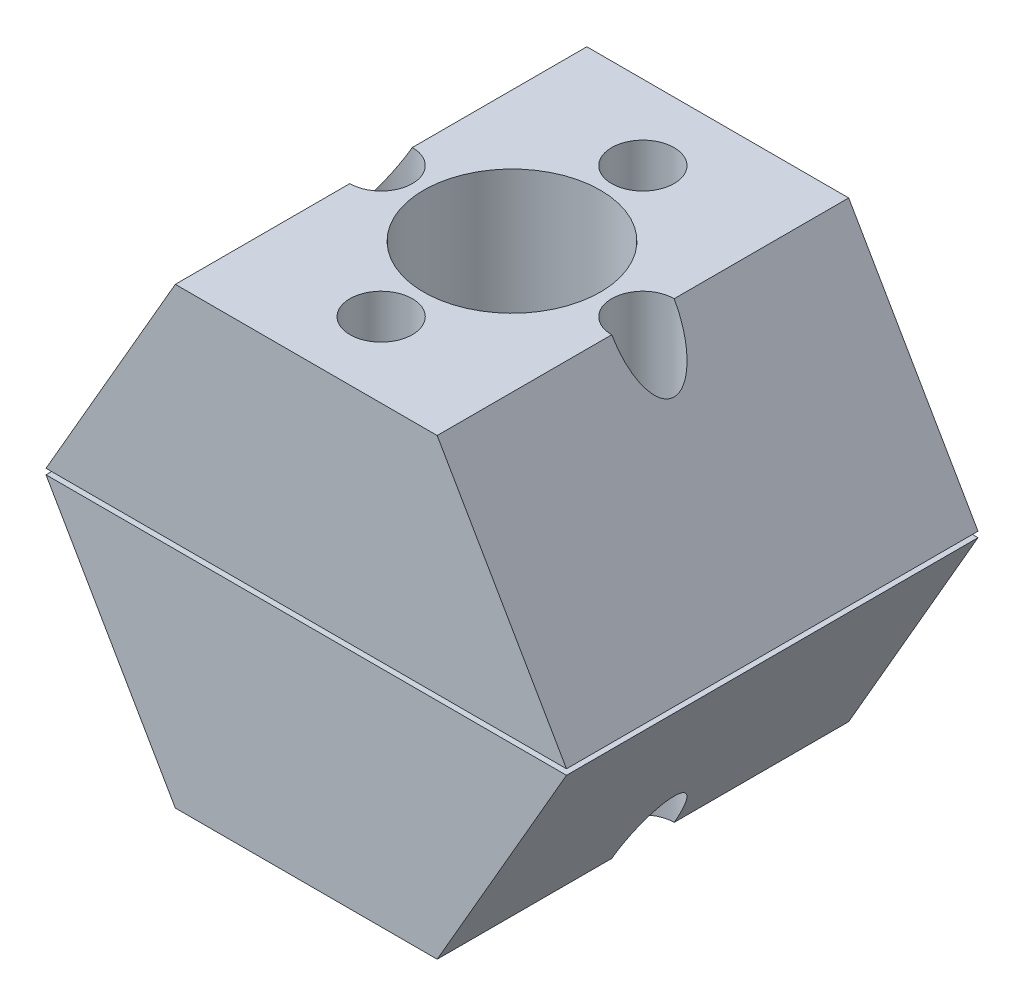
SolidWorks part; units mm, degrees
note: The reader was unsure of these and kept them because the rebuilt part matched: shared geometry of "Sketch1<6>", "Sketch1<7>", "Sketch4<6>", "Sketch3<3>".
ref_plane "Front Plane" through (0, 0, 0) normal (0, 0, 1) x (1, 0, 0)
ref_plane "Top Plane" through (0, 0, 0) normal (0, 1, 0) x (1, 0, 0)
ref_plane "Right Plane" through (0, 0, 0) normal (1, 0, 0) x (0, 0, -1)
sketch "Sketch1" plane through (0, 0, 0) normal (0, 0, 1) x (1, 0, 0)
  line L0 (0, 0) -> (0, 15.5) construction
  line L1 (-5.451, 5.581) -> (-5.451, 15.881)
  line L2 (9.735, 1.5) -> (9.735, 5.2) construction
  line L3 (-5.451, 15.881) -> (5.451, 15.881)
  line L5 (5.451, 15.881) -> (5.451, 5.581)
  line L6 (5.451, 5.581) -> (11.381, 5.581)
  line L7 (11.381, 1.119) -> (11.381, 3.1595)
  line L11 (8.035, 5.2) -> (8.035, 1.5) construction
  line L23 (-9.735, 5.2) -> (-9.735, 1.5) construction
  line L32 (11.381, 1.119) -> (5.451, 1.119)
  line L33 (5.451, -0.381) -> (5.451, 1.119)
  line L34 (5.451, -0.381) -> (-5.451, -0.381)
  line L39 (-5.451, -0.381) -> (-5.451, 1.119)
  line L42 (-5.451, 1.119) -> (-11.381, 1.119)
  line L46 (-11.381, 1.119) -> (-11.381, 3.1595)
  line L47 (-11.381, 5.581) -> (-5.451, 5.581)
  line L48 (-13.97, 3.35) -> (13.97, 3.35) construction
  line L49 (-13.97, -3.55) -> (13.97, -3.55)
  line L50 (4, 15.5) -> (4, 0) construction
  line L51 (6.335, 1.5) -> (6.335, 5.2) construction
  line L52 (-6.335, 1.5) -> (-6.335, 5.2) construction
  line L53 (-4, 15.5) -> (-4, 0) construction
  line L54 (-8.035, 5.2) -> (-8.035, 1.5) construction
  line L55 (6.335, 5.2) -> (9.735, 5.2) construction
  line L56 (-5.07, 15.5) -> (5.07, 15.5) construction
  line L57 (-11, 5.2) -> (-5.07, 5.2) construction
  line L58 (5.07, 0) -> (-5.07, 0) construction
  line L59 (-5.07, 5.2) -> (-5.07, 15.5) construction
  line L60 (-5.07, 1.5) -> (-11, 1.5) construction
  line L61 (5.07, 0) -> (5.07, 1.5) construction
  line L62 (-11, 1.5) -> (-11, 5.2) construction
  line L63 (11, 1.5) -> (11, 5.2) construction
  line L64 (11, 1.5) -> (5.07, 1.5) construction
  line L65 (-9.735, 5.2) -> (-6.335, 5.2) construction
  line L66 (5.07, 15.5) -> (5.07, 5.2) construction
  line L67 (5.07, 5.2) -> (11, 5.2) construction
  line L68 (9.735, 1.5) -> (6.335, 1.5) construction
  line L69 (-5.07, 0) -> (-5.07, 1.5) construction
  line L70 (-6.335, 1.5) -> (-9.735, 1.5)
  line L71 (-13.97, -3.55) -> (-13.97, 19.31)
  line L72 (-13.97, 19.31) -> (13.97, 19.31)
  line L73 (13.97, -3.55) -> (13.97, 19.31)
  line L74 (0, 19.31) -> (0, -3.55) construction
  line L75 (-13.97, 7.88) -> (13.97, 7.88) construction
  line L76 (-11.381, 3.1595) -> (11.381, 3.1595)
  line L77 (-11.381, 3.5405) -> (11.381, 3.5405)
  line L78 (0, 27.0815) -> (0, 38.9219)
  line L79 (-13.97, 3.1595) -> (13.97, 3.1595) construction
  line L80 (-13.97, 3.5405) -> (13.97, 3.5405) construction
  line L81 (-11.381, 3.5405) -> (-11.381, 5.581)
  line L82 (-11.381, 1.119) -> (-11.381, 5.581) construction
  line L83 (11.381, 3.5405) -> (11.381, 5.581)
  line L84 (11.381, 1.119) -> (11.381, 5.581) construction
  line L85 (0, 15.881) -> (0, -0.381)
  line L86 (-11.381, 3.1595) -> (-13.97, 3.1595)
  line L87 (-13.97, 3.1595) -> (-13.97, 3.5405)
  line L88 (-13.97, 3.5405) -> (-11.381, 3.5405)
  line L89 (11.381, 3.5405) -> (13.97, 3.5405)
  line L90 (13.97, 3.5405) -> (13.97, 3.35)
  line L91 (13.97, 3.35) -> (13.97, 3.1595)
  line L92 (13.97, 3.1595) -> (11.381, 3.1595)
  point P64 (0, 3.35)
  point P628 (0, 7.88)
  dimension "D1" = 4
  dimension "D2" = 5.07
  dimension "D3" = 6.335
  dimension "D4" = 8.035
  dimension "D5" = 1.5
  dimension "D6" = 3.35
  dimension "D7" = 4
  dimension "D8" = 5.2
  dimension "D9" = 15.5
  dimension "D10" = 0.381
  dimension "D11" = 3.169
  dimension "D12" = 3.429
  dimension "D13" = 27.94
  dimension "D14" = 0.1905
  dimension "D15" = 0.1905
extrude "Boss-Extrude1" add sketch "Sketch1" along normal mid plane 27.94
revolve "Cut-Revolve8" cut sketch "Sketch1<6>" angle 360 about L74
sketch "Sketch1<6>" plane through (0, 0, 0) normal (0, 0, 1) x (1, 0, 0) same geometry as "Sketch1"
sketch "Sketch4" plane through (0, 0, 13.97) normal (0, 0, 1) x (1, 0, 0)
  line L0 (-13.97, 19.31) -> (13.97, 19.31) construction
  line L1 (-8.89, 18.7479) -> (-17.78, 3.35)
  line L2 (-17.78, 3.35) -> (-8.89, -12.0479)
  line L3 (-8.89, -12.0479) -> (8.89, -12.0479)
  line L4 (8.89, -12.0479) -> (17.78, 3.35)
  line L5 (17.78, 3.35) -> (8.89, 18.7479)
  line L6 (8.89, 18.7479) -> (-8.89, 18.7479)
  line L8 (-25.9513, 3.5405) -> (25.9513, 3.5405)
  line L9 (-25.9513, 3.5405) -> (-25.9513, 3.1595)
  line L10 (-25.9513, 3.1595) -> (25.9513, 3.1595)
  line L11 (13.97, 3.1595) -> (-13.97, 3.1595)
  line L12 (-13.97, 3.1595) -> (-13.97, -3.55)
  line L13 (-13.97, -3.55) -> (13.97, -3.55)
  line L14 (13.97, -3.55) -> (13.97, 3.1595)
  line L15 (13.97, 3.1595) -> (-13.97, 3.1595)
  line L16 (-13.97, 3.1595) -> (-13.97, -3.55)
  line L17 (-13.97, -3.55) -> (13.97, -3.55)
  line L18 (13.97, -3.55) -> (13.97, 3.1595)
  line L19 (-13.97, 19.31) -> (-13.97, 3.5405)
  line L20 (-13.97, 3.5405) -> (13.97, 3.5405)
  line L21 (13.97, 3.5405) -> (13.97, 19.31)
  line L22 (13.97, 19.31) -> (-13.97, 19.31)
  line L23 (-13.97, 19.31) -> (-13.97, 3.5405)
  line L24 (-13.97, 3.5405) -> (13.97, 3.5405)
  line L25 (13.97, 3.5405) -> (13.97, 19.31)
  line L26 (13.97, 19.31) -> (-13.97, 19.31)
  line L27 (25.9513, 3.5405) -> (25.9513, 3.1595)
  line L28 (-25.9513, 3.5405) -> (25.9513, 3.1595) construction
  line L29 (-25.9513, 3.1595) -> (25.9513, 3.5405) construction
  circle A0 centre (0, 3.35) radius 15.3979 construction
  circle A1 centre (0, 3.35) radius 23.3982
  line M2 (-13.97, 19.31) -> (-13.97, 3.5405)
  line M4 (13.97, 3.5405) -> (13.97, 19.31)
  line M5 (13.97, 19.31) -> (-13.97, 19.31)
  dimension "D1" = 0
  dimension "D2" = 0
extrude "Body Shaping - Square" cut sketch "Sketch4" against normal blind 34.417 contours A1 L18 L17 L4 L3 L2 L16 L1 L5 M2 M5 M4 | L16 L17 L2 | L17 L18 L4 | L6 L5 L1 M4 M5 M2
revolve "Cut-Revolve9" cut sketch "Sketch1<7>" angle 360 about L85
sketch "Sketch1<7>" plane through (0, 0, 0) normal (0, 0, 1) x (1, 0, 0) same geometry as "Sketch1"
extrude "Making things hexagonal" add sketch "Sketch4<6>" against normal up to surface (27.94 mm away) contours L18 L4 L10 | L8 L5 M4 | L17 L2 L3 L4 | L16 L10 L2 | L1 L8 M2
sketch "Sketch4<6>" plane through (0, 0, 13.97) normal (0, 0, 1) x (1, 0, 0) same geometry as "Sketch4"
sketch "Sketch2" plane through (0, -12.0479, 0) normal (0, 1, 0) x (1, 0, 0)
  circle A0 centre (0, 0) radius 5.451 construction
  circle A1 centre (0, 0) radius 6
  dimension "D1" = 12
extrude "Through Hole for ACME Rod" cut sketch "Sketch2" along normal through all contours A1
sketch "Sketch3" plane through (0, -12.0479, 0) normal (0, -1, 0) x (1, 0, 0)
  line L1 (-9.735, 0) -> (-8.035, 0) construction
  line L2 (-11, 0) -> (-5.07, 0) construction
  line L3 (8.89, -13.97) -> (8.89, 13.97) construction
  circle A0 centre (-8.885, 0) radius 0.85
  circle A1 centre (0, 8.885) radius 0.85
  circle A2 centre (8.885, 0) radius 0.85
  circle A3 centre (0, -8.885) radius 0.85
  circle A4 centre (-8.885, 0) radius 2.12
  circle A5 centre (0, 8.885) radius 2.12
  circle A6 centre (8.885, 0) radius 2.12
  circle A7 centre (0, -8.885) radius 2.12
  point P20 (0, 0)
  line M23 (8.89, -13.97) -> (8.89, 13.97)
  line M25 (-8.89, 13.97) -> (-8.89, -13.97)
  dimension "D1" = 0.005
  dimension "D3" = 1.27
  dimension "D2" = 4
extrude "Bolt Holes" cut sketch "Sketch3" against normal through all both and the other way through all contours L1 A0 | A0 L1 | A1 | A2 | A3 | A2 M23 | A0 L1 M25 | L1 A0 M25
extrude "Cut-Extrude4" cut sketch "Sketch3<3>" against normal blind 9.525 contours A6 | A7 | A4 | A5
sketch "Sketch3<3>" plane through (0, -12.0479, 0) normal (0, -1, 0) x (1, 0, 0) same geometry as "Sketch3"
sketch "Sketch5" plane through (0, 18.7479, 0) normal (0, 1, 0) x (1, 0, 0)
  circle A0 centre (0, 8.885) radius 2.12 construction
  circle A1 centre (-8.885, 0) radius 2.12 construction
  circle A2 centre (8.885, 0) radius 2.12 construction
  circle A3 centre (0, -8.885) radius 2.12 construction
  circle A4 centre (0, 8.885) radius 2.12
  circle A5 centre (-8.885, 0) radius 2.12
  circle A6 centre (8.885, 0) radius 2.12
  circle A7 centre (0, -8.885) radius 2.12
extrude "Cut-Extrude5" cut sketch "Sketch5" against normal blind 9.525
